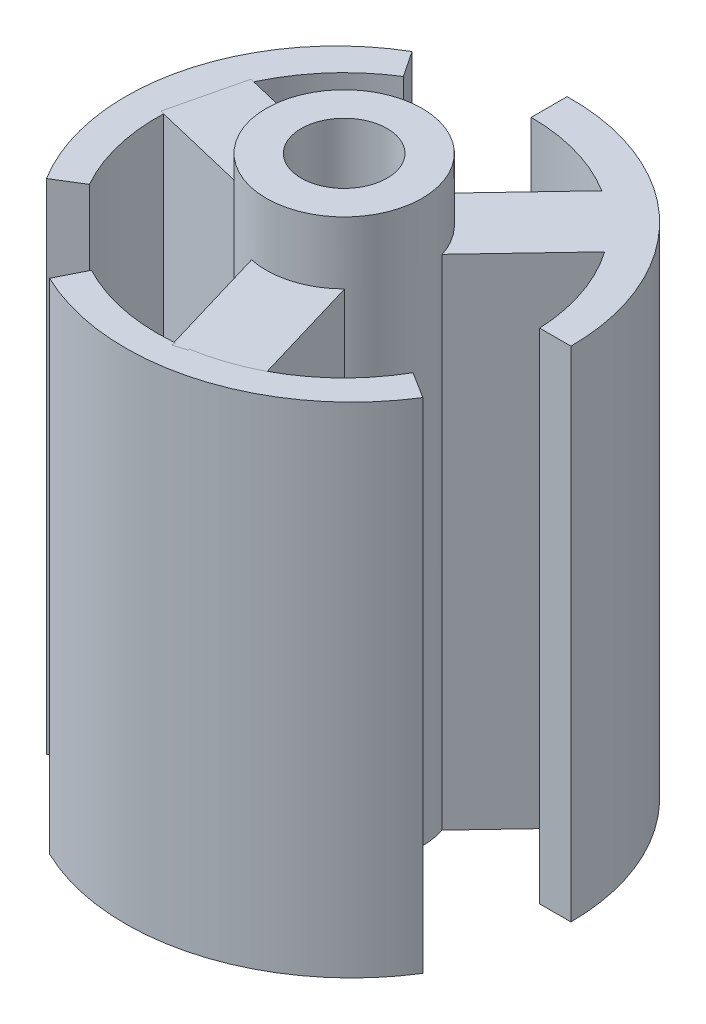
SolidWorks part; units mm, degrees
ref_plane "Front Plane" through (0, 0, 0) normal (0, 0, 1) x (1, 0, 0)
ref_plane "Top Plane" through (0, 0, 0) normal (0, 1, 0) x (1, 0, 0)
ref_plane "Right Plane" through (0, 0, 0) normal (1, 0, 0) x (0, 0, -1)
sketch "Sketch11" plane through (0, 0, 0) normal (0, 1, 0) x (1, 0, 0)
  line L0 (-15.1905, -8.6889) -> (0, 0.7002)
  line L1 (0, 0.7002) -> (-8.1366, -15.4934)
  line L2 (15.1201, -8.8109) -> (0, 0.7002)
  line L3 (0, 0.7002) -> (17.486, 0.7002)
  line L4 (0, 0.7002) -> (-9.3494, 14.7932)
  line L5 (0, 0.7002) -> (0, 17.8816)
  arc A3 (15.1201, -8.8109) -> (-8.1366, -15.4934) centre (-0.2456, 0.8547) cw
  arc A5 (-15.1905, -8.6889) -> (-9.3494, 14.7932) centre (-0.8078, 0.2009) cw
  arc A6 (17.486, 0.7002) -> (0, 17.8816) centre (0.3019, 0.7002) ccw
  circle A7 centre (0, 0.7002) radius 16.25
  point P11 (0, 0)
sketch "Sketch12" plane through (0, 0, 0) normal (0, 1, 0) x (1, 0, 0)
  circle A0 centre (0, 0) radius 15
extrude "Boss-Extrude6" add sketch "Sketch11" along normal blind 40 contours L0 A5 L4 | L2 A3 L1 | L3 A6 L5
extrude "Cut-Extrude9" cut sketch "Sketch12" along normal blind 40 contours A0
sketch "Sketch17" plane through (0, 0, 0) normal (0, 1, 0) x (1, 0, 0)
  line L0 (12.4951, 8.8245) -> (8.1399, 12.9515)
  line L1 (12.4951, 8.8245) -> (2.1256, -2.1183)
  line L2 (8.1399, 12.9515) -> (-2.2296, 2.0087)
  line L3 (2.1256, -2.1183) -> (-2.2296, 2.0087)
  line L4 (-2.8974, -0.7817) -> (2.8543, 0.9265)
  line L5 (1.3947, -15.2333) -> (-2.8974, -0.7817)
  line L6 (1.3947, -15.2333) -> (7.1464, -13.5251)
  line L7 (7.1464, -13.5251) -> (2.8543, 0.9265)
  line L8 (0.7717, 2.9) -> (-0.6248, -2.9352)
  line L9 (-13.8898, 6.4089) -> (0.7717, 2.9)
  line L10 (-13.8898, 6.4089) -> (-15.2863, 0.5736)
  line L11 (-15.2863, 0.5736) -> (-0.6248, -2.9352)
  arc A1 (14.9836, 0.7002) -> (0, 15) centre (0, 0) ccw construction
  point P18 (0, 0)
  dimension "D1" = 3
extrude "Boss-Extrude8" add sketch "Sketch17" along normal blind 40 separate body contours L2 L9 L8 L4 L7 L1 L0 | L4 L8 L3 L1 L7 | L9 L2 L3 L4 L8 | L11 L5 L6 L7 L1 L3 L8 | L5 L11 L8 L3 L4 | L10 L11 L5 L4 L3 L2 L9 | L4 L7 L6 L5 region at (5.7685, 0, -6.0874) region at (2.3876, 0, 8.0393) region at (1.914, 0, 0.4581) region at (-0.5603, 0, -1.8866) region at (-8.1561, 0, -1.9519) region at (-1.3537, 0, 1.4286)
sketch "Sketch18" plane through (0, 0, 0) normal (0, 1, 0) x (1, 0, 0)
  circle A0 centre (0, 0) radius 6.25
extrude "Boss-Extrude9" add sketch "Sketch18" along normal blind 45
sketch "Sketch21" plane through (0, 0, 0) normal (0, 1, 0) x (1, 0, 0)
  circle A0 centre (0, 0) radius 16.25
sketch "Sketch22" plane through (0, 0, 0) normal (0, 1, 0) x (1, 0, 0)
  circle A0 centre (0, 0) radius 3.45
extrude "Cut-Extrude13" cut sketch "Sketch22" along normal through all
